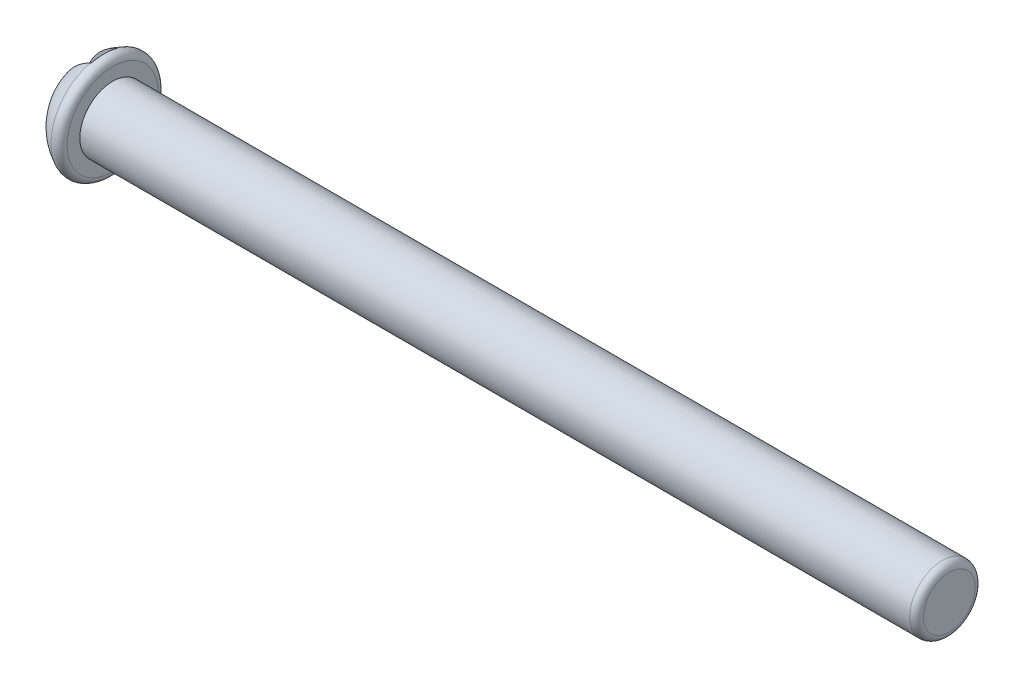
SolidWorks part; units mm, degrees
ref_plane "Front Plane" through (0, 0, 0) normal (0, 0, 1) x (1, 0, 0)
ref_plane "Top Plane" through (0, 0, 0) normal (0, 1, 0) x (1, 0, 0)
ref_plane "Right Plane" through (0, 0, 0) normal (1, 0, 0) x (0, 0, -1)
sketch "Sketch1" plane through (0, 0, 0) normal (0, 1, 0) x (1, 0, 0)
  line L0 (0, 0) -> (25.5, 0)
  line L1 (25.5, 0) -> (25.5, 0.95)
  line L2 (25.5, 0.95) -> (1.25, 0.95)
  line L3 (1.25, 0.95) -> (1.25, 1.6)
  arc A0 (0, 0) -> (1.25, 1.6) centre (1.649, 0) cw
  dimension "D1" = 1.6
  dimension "D2" = 1.25
  dimension "D3" = 25.5
  dimension "D4" = 0.95
revolve "Revolve1" add sketch "Sketch1" angle 360 about L0
sketch "Sketch2" plane through (0, 0, 0) normal (1, 0, 0) x (0, 0, -1)
  line L0 (-0.1433, -0.7362) -> (-0.375, -1.9259) construction
  line L1 (0.375, -1.9259) -> (-0.375, -1.9259)
  line L2 (0.375, -1.9259) -> (0.375, -0.6495)
  line L3 (0.375, 1.9259) -> (-0.375, 1.9259)
  line L4 (-0.375, -1.9259) -> (-0.375, -0.6495)
  line L6 (0.375, 1.9259) -> (0.1433, 0.7362) construction
  line L8 (0.375, 0.6495) -> (0.375, 1.9259)
  line L9 (-0.375, 0.6495) -> (-0.375, 1.9259)
  arc A0 (-0.375, 0.6495) -> (-0.375, -0.6495) centre (0, 0) ccw
  arc A1 (0.375, -0.6495) -> (0.375, 0.6495) centre (0, 0) ccw
  point P0 (0, 0)
  dimension "D2" = 1.5
  dimension "D1" = 0.75
extrude "Cut-Extrude1" cut sketch "Sketch2" along normal blind 1
fillet "Fillet1" radius 0.2 2 edges at (25.5, 0, 0.95) (1.25, 0, 1.6)
